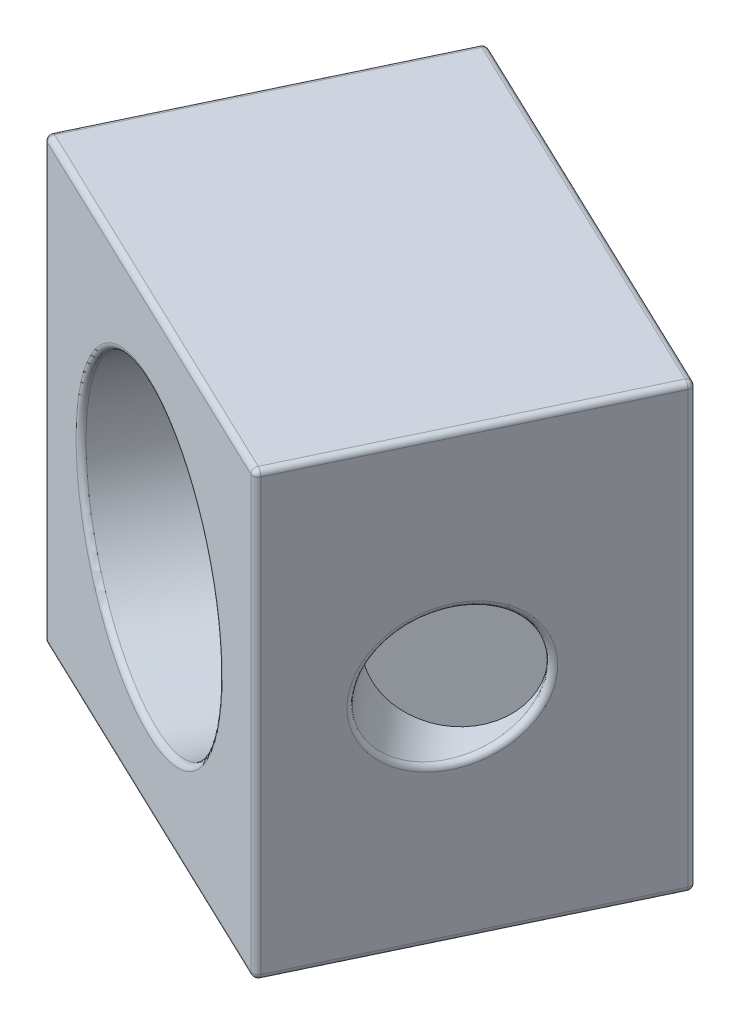
SolidWorks part; units mm, degrees
ref_plane "Front Plane" through (0, 0, 0) normal (0, 0, 1) x (1, 0, 0)
ref_plane "Top Plane" through (0, 0, 0) normal (0, 1, 0) x (1, 0, 0)
ref_plane "Right Plane" through (0, 0, 0) normal (1, 0, 0) x (0, 0, -1)
sketch "Sketch1" plane through (0, 0, 0) normal (0, 1, 0) x (1, 0, 0)
  line L0 (0, 0) -> (640, 0) construction
  line L1 (0, 0) -> (591.2829, 244.9174)
  line L2 (0, 0) -> (591.2829, -244.9174)
  line L3 (0, 0) -> (244.9174, -591.2829)
  line L4 (0, 0) -> (-244.9174, -591.2829)
  line L5 (0, 0) -> (-591.2829, -244.9174)
  line L6 (0, 0) -> (-591.2829, 244.9174)
  line L7 (0, 0) -> (-244.9174, 591.2829)
  line L8 (0, 0) -> (244.9174, 591.2829)
  line L9 (0, 145) -> (55, 145) construction
  line L10 (0, 0) -> (100, 0) construction
  line L11 (0, 0) -> (0, 145) construction
  line L14 (100, 0) -> (100, 145) construction
  circle A0 centre (0, 0) radius 640 construction
  point P15 (0, 0)
  dimension "D1" = 1280
  dimension "D2" = 22.5
  dimension "D4" = 145
  dimension "D5" = 100
  dimension "D6" = 55
  dimension "D3" = 8
sketch "Sketch2" plane through (0, 0, 0) normal (0, 1, 0) x (1, 0, 0)
  line L0 (-486.9956, 169.5033) -> (-66.9956, 169.5033) construction
  line L1 (-188.7141, -86.1278) -> (-188.7141, 241.8722) construction
  line L2 (525.6625, -1048.8053) -> (466.9027, -726.1115) construction
sketch "Sketch3" plane through (0, 0, 0) normal (0, 1, 0) x (1, 0, 0)
  line L0 (0, 0) -> (381.2468, 0) construction
  line L5 (0, 0) -> (0, 199.4415) construction
  line L6 (-10.2736, 158.9263) -> (10.2736, 158.9263)
  line L7 (10.2736, 158.9263) -> (13.1995, 163.9003)
  line L8 (13.1995, 163.9003) -> (45.5131, 148.2994)
  line L9 (45.5131, 148.2994) -> (66.2904, 80.9335)
  line L10 (66.2904, 80.9335) -> (73.8622, 80.9335)
  line L11 (73.8622, 80.9335) -> (86.8684, 42.4396)
  line L12 (86.8684, 42.4396) -> (86.8684, 30.0712)
  line L13 (86.8684, 30.0712) -> (81.3965, 24.5993)
  line L14 (81.3965, 24.5993) -> (81.3965, -24.5993)
  line L15 (-5.8349, 67.4929) -> (5.8349, 67.4929) construction
  line L16 (16.6008, 64.1674) -> (16.6008, 27.6557) construction
  line L17 (16.6008, 27.6557) -> (13.2646, 22.809) construction
  line L18 (13.2646, 22.809) -> (13.2646, -22.809) construction
  line L19 (5.8349, 128.0146) -> (5.8349, 107.4452)
  line L22 (5.8349, 107.4452) -> (9.2702, 107.4452)
  line L25 (9.2702, 107.4452) -> (10.663, 103.7163)
  line L26 (10.663, 103.7163) -> (20.7578, 101.0699)
  line L27 (20.7578, 101.0699) -> (32.199, 111.7601)
  line L28 (32.199, 111.7601) -> (32.199, 123.5038)
  line L29 (32.199, 123.5038) -> (24.9078, 123.5038)
  line L30 (24.9078, 123.5038) -> (13.8412, 132.5856)
  line L31 (13.8412, 132.5856) -> (9.2702, 132.5856)
  line L32 (9.2702, 132.5856) -> (5.8349, 128.0146)
  line L33 (41.9414, 39.7891) -> (51.4866, 54.1602)
  line L34 (51.4866, 54.1602) -> (55.4027, 54.1602)
  line L35 (55.4027, 54.1602) -> (58.1637, 51.3993)
  line L36 (58.1637, 51.3993) -> (58.1637, 43.1872)
  line L37 (58.1637, 43.1872) -> (66.3555, 28.462)
  line L38 (66.3555, 28.462) -> (66.3555, 24.0728)
  line L39 (66.3555, 24.0728) -> (62.2596, 17.9061)
  line L40 (62.2596, 17.9061) -> (47.8497, 18.1669)
  line L41 (47.8497, 18.1669) -> (41.9414, 27.1878)
  line L42 (41.9414, 27.1878) -> (41.9414, 39.7891)
  line L43 (-41.9414, 27.1878) -> (-41.9414, 39.7891)
  line L44 (-47.8497, 18.1669) -> (-41.9414, 27.1878)
  line L45 (-62.2596, 17.9061) -> (-47.8497, 18.1669)
  line L46 (-66.3555, 24.0728) -> (-62.2596, 17.9061)
  line L47 (-66.3555, 28.462) -> (-66.3555, 24.0728)
  line L48 (-58.1637, 43.1872) -> (-66.3555, 28.462)
  line L49 (-58.1637, 51.3993) -> (-58.1637, 43.1872)
  line L50 (-55.4027, 54.1602) -> (-58.1637, 51.3993)
  line L51 (-51.4866, 54.1602) -> (-55.4027, 54.1602)
  line L52 (-41.9414, 39.7891) -> (-51.4866, 54.1602)
  line L53 (-9.2702, 132.5856) -> (-5.8349, 128.0146)
  line L54 (-13.8412, 132.5856) -> (-9.2702, 132.5856)
  line L55 (-24.9078, 123.5038) -> (-13.8412, 132.5856)
  line L56 (-32.199, 123.5038) -> (-24.9078, 123.5038)
  line L57 (-32.199, 111.7601) -> (-32.199, 123.5038)
  line L58 (-20.7578, 101.0699) -> (-32.199, 111.7601)
  line L59 (-10.663, 103.7163) -> (-20.7578, 101.0699)
  line L60 (-9.2702, 107.4452) -> (-10.663, 103.7163)
  line L61 (-5.8349, 107.4452) -> (-9.2702, 107.4452)
  line L62 (-5.8349, 128.0146) -> (-5.8349, 107.4452)
  line L63 (-13.2646, 22.809) -> (-13.2646, -22.809) construction
  line L64 (-16.6008, 27.6557) -> (-13.2646, 22.809) construction
  line L65 (-16.6008, 64.1674) -> (-16.6008, 27.6557) construction
  line L66 (-81.3965, 24.5993) -> (-81.3965, -24.5993)
  line L67 (-86.8684, 30.0712) -> (-81.3965, 24.5993)
  line L68 (-86.8684, 42.4396) -> (-86.8684, 30.0712)
  line L69 (-73.8622, 80.9335) -> (-86.8684, 42.4396)
  line L70 (-66.2904, 80.9335) -> (-73.8622, 80.9335)
  line L71 (-45.5131, 148.2994) -> (-66.2904, 80.9335)
  line L72 (-13.1995, 163.9003) -> (-45.5131, 148.2994)
  line L73 (-10.2736, 158.9263) -> (-13.1995, 163.9003)
  line L74 (-10.2736, -158.9263) -> (-13.1995, -163.9003)
  line L75 (-13.1995, -163.9003) -> (-45.5131, -148.2994)
  line L76 (-45.5131, -148.2994) -> (-66.2904, -80.9335)
  line L77 (-66.2904, -80.9335) -> (-73.8622, -80.9335)
  line L78 (-73.8622, -80.9335) -> (-86.8684, -42.4396)
  line L79 (-86.8684, -42.4396) -> (-86.8684, -30.0712)
  line L80 (-86.8684, -30.0712) -> (-81.3965, -24.5993)
  line L81 (-16.6008, -64.1674) -> (-16.6008, -27.6557) construction
  line L82 (-16.6008, -27.6557) -> (-13.2646, -22.809) construction
  line L83 (-5.8349, -128.0146) -> (-5.8349, -107.4452)
  line L84 (-5.8349, -107.4452) -> (-9.2702, -107.4452)
  line L85 (-9.2702, -107.4452) -> (-10.663, -103.7163)
  line L86 (-10.663, -103.7163) -> (-20.7578, -101.0699)
  line L87 (-20.7578, -101.0699) -> (-32.199, -111.7601)
  line L88 (-32.199, -111.7601) -> (-32.199, -123.5038)
  line L89 (-32.199, -123.5038) -> (-24.9078, -123.5038)
  line L90 (-24.9078, -123.5038) -> (-13.8412, -132.5856)
  line L91 (-13.8412, -132.5856) -> (-9.2702, -132.5856)
  line L92 (-9.2702, -132.5856) -> (-5.8349, -128.0146)
  line L93 (-41.9414, -39.7891) -> (-51.4866, -54.1602)
  line L94 (-51.4866, -54.1602) -> (-55.4027, -54.1602)
  line L95 (-55.4027, -54.1602) -> (-58.1637, -51.3993)
  line L96 (-58.1637, -51.3993) -> (-58.1637, -43.1872)
  line L97 (-58.1637, -43.1872) -> (-66.3555, -28.462)
  line L98 (-66.3555, -28.462) -> (-66.3555, -24.0728)
  line L99 (-66.3555, -24.0728) -> (-62.2596, -17.9061)
  line L100 (-62.2596, -17.9061) -> (-47.8497, -18.1669)
  line L101 (-47.8497, -18.1669) -> (-41.9414, -27.1878)
  line L102 (-41.9414, -27.1878) -> (-41.9414, -39.7891)
  line L103 (41.9414, -27.1878) -> (41.9414, -39.7891)
  line L104 (47.8497, -18.1669) -> (41.9414, -27.1878)
  line L105 (62.2596, -17.9061) -> (47.8497, -18.1669)
  line L106 (66.3555, -24.0728) -> (62.2596, -17.9061)
  line L107 (66.3555, -28.462) -> (66.3555, -24.0728)
  line L108 (58.1637, -43.1872) -> (66.3555, -28.462)
  line L109 (58.1637, -51.3993) -> (58.1637, -43.1872)
  line L110 (55.4027, -54.1602) -> (58.1637, -51.3993)
  line L111 (51.4866, -54.1602) -> (55.4027, -54.1602)
  line L112 (41.9414, -39.7891) -> (51.4866, -54.1602)
  line L113 (9.2702, -132.5856) -> (5.8349, -128.0146)
  line L114 (13.8412, -132.5856) -> (9.2702, -132.5856)
  line L115 (24.9078, -123.5038) -> (13.8412, -132.5856)
  line L116 (32.199, -123.5038) -> (24.9078, -123.5038)
  line L117 (32.199, -111.7601) -> (32.199, -123.5038)
  line L118 (20.7578, -101.0699) -> (32.199, -111.7601)
  line L119 (10.663, -103.7163) -> (20.7578, -101.0699)
  line L120 (9.2702, -107.4452) -> (10.663, -103.7163)
  line L121 (5.8349, -107.4452) -> (9.2702, -107.4452)
  line L122 (5.8349, -128.0146) -> (5.8349, -107.4452)
  line L123 (16.6008, -27.6557) -> (13.2646, -22.809) construction
  line L124 (16.6008, -64.1674) -> (16.6008, -27.6557) construction
  line L125 (-5.8349, -67.4929) -> (5.8349, -67.4929) construction
  line L126 (86.8684, -30.0712) -> (81.3965, -24.5993)
  line L127 (86.8684, -42.4396) -> (86.8684, -30.0712)
  line L128 (73.8622, -80.9335) -> (86.8684, -42.4396)
  line L129 (66.2904, -80.9335) -> (73.8622, -80.9335)
  line L130 (45.5131, -148.2994) -> (66.2904, -80.9335)
  line L131 (13.1995, -163.9003) -> (45.5131, -148.2994)
  line L132 (10.2736, -158.9263) -> (13.1995, -163.9003)
  line L133 (-10.2736, -158.9263) -> (10.2736, -158.9263)
  line L134 (-5.3457, 68.4929) -> (5.3457, 68.4929)
  line L135 (17.6008, 64.1674) -> (17.6008, 27.3448)
  line L136 (17.6008, 27.3448) -> (14.2646, 22.498)
  line L137 (14.2646, 22.498) -> (14.2646, -22.498)
  line L138 (-17.6008, 64.1674) -> (-17.6008, 27.3448)
  line L139 (-17.6008, 27.3448) -> (-14.2646, 22.498)
  line L140 (-5.3457, 68.4929) -> (5.3457, 68.4929) construction
  line L141 (14.2646, 22.498) -> (14.2646, -22.498) construction
  line L142 (17.6008, -27.3448) -> (14.2646, -22.498) construction
  line L143 (17.6008, -64.1674) -> (17.6008, -27.3448) construction
  line L144 (-14.2646, 22.498) -> (-14.2646, -22.498)
  line L145 (17.6008, -64.1674) -> (17.6008, -27.3448)
  line L146 (17.6008, -27.3448) -> (14.2646, -22.498)
  line L147 (-17.6008, -27.3448) -> (-14.2646, -22.498)
  line L148 (-17.6008, -64.1674) -> (-17.6008, -27.3448)
  line L149 (-5.3457, -68.4929) -> (5.3457, -68.4929)
  arc A0 (5.8349, 67.4929) -> (16.6008, 64.0252) centre (10.663, 64.0364) cw construction
  arc A5 (-5.8349, 67.4929) -> (-16.6008, 64.0252) centre (-10.663, 64.0364) ccw construction
  arc A6 (-5.8349, -67.4929) -> (-16.6008, -64.0252) centre (-10.663, -64.0364) cw construction
  arc A7 (5.8349, -67.4929) -> (16.6008, -64.0252) centre (10.663, -64.0364) ccw construction
  arc A8 (-5.3457, 68.4929) -> (-17.6008, 64.0234) centre (-10.663, 64.0364) ccw
  arc A9 (5.3457, 68.4929) -> (17.6008, 64.0234) centre (10.663, 64.0364) cw
  arc A10 (-5.3457, 68.4929) -> (-17.6008, 64.0234) centre (-10.663, 64.0364) ccw construction
  arc A11 (5.3457, -68.4929) -> (17.6008, -64.0234) centre (10.663, -64.0364) ccw
  arc A12 (-5.3457, -68.4929) -> (-17.6008, -64.0234) centre (-10.663, -64.0364) cw
  ellipse E0 centre (11.3851, 149.6854) end of major axis (12.0553, 155.2702) minor radius 3.0047
  ellipse E1 centre (33.6925, 82.363) end of major axis (41.1096, 88.3895) minor radius 4.3287
  ellipse E2 centre (44.8955, 74.0187) end of major axis (51.4866, 79.374) minor radius 4.6847
  ellipse E3 centre (66.3555, 66.447) end of major axis (67.1471, 72.2416) minor radius 3.5711
  ellipse E4 centre (-66.3555, 66.447) end of major axis (-67.1471, 72.2416) minor radius 3.5711
  ellipse E5 centre (-44.8955, 74.0187) end of major axis (-51.4866, 79.374) minor radius 4.6847
  ellipse E6 centre (-33.6925, 82.363) end of major axis (-41.1096, 88.3895) minor radius 4.3287
  ellipse E7 centre (-11.3851, 149.6854) end of major axis (-12.0553, 155.2702) minor radius 3.0047
  ellipse E8 centre (-11.3851, -149.6854) end of major axis (-12.0553, -155.2702) minor radius 3.0047
  ellipse E9 centre (-33.6925, -82.363) end of major axis (-41.1096, -88.3895) minor radius 4.3287
  ellipse E10 centre (-44.8955, -74.0187) end of major axis (-51.4866, -79.374) minor radius 4.6847
  ellipse E11 centre (-66.3555, -66.447) end of major axis (-67.1471, -72.2416) minor radius 3.5711
  ellipse E12 centre (66.3555, -66.447) end of major axis (67.1471, -72.2416) minor radius 3.5711
  ellipse E13 centre (44.8955, -74.0187) end of major axis (51.4866, -79.374) minor radius 4.6847
  ellipse E14 centre (33.6925, -82.363) end of major axis (41.1096, -88.3895) minor radius 4.3287
  ellipse E15 centre (11.3851, -149.6854) end of major axis (12.0553, -155.2702) minor radius 3.0047
  point P117 (0, 67.4929)
  point P126 (0, 158.9263)
  point P180 (0, -158.9263)
  point P181 (0, -67.4929)
  point P190 (-81.3965, 0)
  point P193 (-13.2646, 0)
  point P234 (13.2646, 0)
  point P237 (81.3965, 0)
  point P261 (0, 68.4929)
  point P271 (14.2646, 0)
  point P274 (-14.2646, 0)
  dimension "D1" = 1
sketch "Sketch4" plane through (0, 0, 0) normal (0, 1, 0) x (1, 0, 0)
  line L0 (0, 0) -> (81.2255, 0) construction
  line L1 (0, 0) -> (0, 97.3086) construction
  line L2 (0, 0) -> (0, 199.4415) construction
  line L3 (-10.1399, 86.6928) -> (10.1399, 86.6928)
  line L4 (10.1399, 86.6928) -> (16.0235, 80.8091)
  line L5 (16.0235, 80.8091) -> (23.9736, 57.3032)
  line L6 (23.9736, 57.3032) -> (23.9736, 47.8894)
  line L7 (23.9736, 47.8894) -> (21.6776, 47.8894)
  line L8 (21.6776, 47.8894) -> (21.6776, 27.2256)
  line L9 (21.6776, 27.2256) -> (27.5382, 22.1416)
  line L10 (27.5382, 22.1416) -> (27.5382, 14.9676)
  line L11 (27.5382, 14.9676) -> (23.9736, 10.8585)
  line L12 (23.9736, 10.8585) -> (23.9736, -10.8585)
  line L13 (-23.9736, 10.8585) -> (-23.9736, -10.8585)
  line L14 (-27.5382, 14.9676) -> (-23.9736, 10.8585)
  line L15 (-27.5382, 22.1416) -> (-27.5382, 14.9676)
  line L16 (-21.6776, 27.2256) -> (-27.5382, 22.1416)
  line L17 (-21.6776, 47.8894) -> (-21.6776, 27.2256)
  line L18 (-23.9736, 47.8894) -> (-21.6776, 47.8894)
  line L19 (-23.9736, 57.3032) -> (-23.9736, 47.8894)
  line L20 (-16.0235, 80.8091) -> (-23.9736, 57.3032)
  line L21 (-10.1399, 86.6928) -> (-16.0235, 80.8091)
  line L22 (-10.1399, -86.6928) -> (-16.0235, -80.8091)
  line L23 (-16.0235, -80.8091) -> (-23.9736, -57.3032)
  line L24 (-23.9736, -57.3032) -> (-23.9736, -47.8894)
  line L25 (-23.9736, -47.8894) -> (-21.6776, -47.8894)
  line L26 (-21.6776, -47.8894) -> (-21.6776, -27.2256)
  line L27 (-21.6776, -27.2256) -> (-27.5382, -22.1416)
  line L28 (-27.5382, -22.1416) -> (-27.5382, -14.9676)
  line L29 (-27.5382, -14.9676) -> (-23.9736, -10.8585)
  line L30 (27.5382, -14.9676) -> (23.9736, -10.8585)
  line L31 (27.5382, -22.1416) -> (27.5382, -14.9676)
  line L32 (21.6776, -27.2256) -> (27.5382, -22.1416)
  line L33 (21.6776, -47.8894) -> (21.6776, -27.2256)
  line L34 (23.9736, -47.8894) -> (21.6776, -47.8894)
  line L35 (23.9736, -57.3032) -> (23.9736, -47.8894)
  line L36 (16.0235, -80.8091) -> (23.9736, -57.3032)
  line L37 (10.1399, -86.6928) -> (16.0235, -80.8091)
  line L38 (-10.1399, -86.6928) -> (10.1399, -86.6928)
  point P3 (0, -86.6928)
  point P27 (0, 86.6928)
  point P37 (-23.9736, 0)
  point P38 (23.9736, 0)
sketch "Sketch5" plane through (0, 0, 0) normal (0, 1, 0) x (1, 0, 0)
  line L0 (0, 68.4929) -> (0, 86.6928) construction
  line L1 (15.4511, 110) -> (223.3697, 546.0887)
  line L2 (0, 0) -> (0, 251.8084) construction
  line L3 (0, 110) -> (47.9221, 110) construction
  line L5 (244.9174, 616.9519) -> (262.4572, 609.0616) construction
  line L6 (262.4572, 609.0616) -> (269.1565, 599.6825) construction
  line L7 (269.1565, 599.6825) -> (256.4381, 571.4103) construction
  line L8 (256.4381, 571.4103) -> (244.9174, 563.1812) construction
  line L9 (244.9174, 563.1812) -> (221.08, 517.0826) construction
  line L10 (221.08, 517.0826) -> (201.6817, 527.1134) construction
  line L11 (201.6817, 527.1134) -> (221.6088, 571.4103) construction
  line L12 (221.6088, 571.4103) -> (218.2415, 584.6462) construction
  line L13 (218.2415, 584.6462) -> (232.4366, 616.2011) construction
  line L14 (232.4366, 616.2011) -> (244.9174, 616.9519) construction
  line L15 (244.9174, 591.2829) -> (309.3694, 564.586) construction
  line L16 (269.6266, 526.9284) -> (173.6132, 566.6985) construction
  line L18 (0, 0) -> (107.3069, 0) construction
  dimension "D1" = 110
  dimension "D2" = 50
sketch "Sketch6" plane through (0, 0, 0) normal (0, 1, 0) x (1, 0, 0)
  line L1 (27.9119, 24.7148) -> (544.6401, 226.6863)
  circle A0 centre (0, 0) radius 640 construction
  circle A1 centre (0, 0) radius 640 construction
  circle A3 centre (0, 0) radius 589.9318 construction
  dimension "D1" = 50.0682
sketch "Sketch19" plane through (0, 0, 0) normal (0, 1, 0) x (1, 0, 0)
  line L0 (128.4599, 309.2664) -> (271.805, 137.4916) construction
  line L1 (128.4599, 309.2664) -> (95.7387, 324.8672) construction
  line L2 (128.4599, 309.2664) -> (131.8448, 307.6525) construction
  line L3 (-2.602, 118.6074) -> (205.3166, 554.696)
  line L4 (-2.602, 118.6074) -> (205.3166, 554.696) construction
  line L5 (26.7343, 104.6204) -> (234.6528, 540.7091)
  line L6 (26.7343, 104.6204) -> (234.6528, 540.7091) construction
  line L7 (4.1679, 115.3796) -> (212.0865, 551.4683)
  line L8 (4.1679, 115.3796) -> (212.0865, 551.4683) construction
  line L9 (20.631, 43.3425) -> (537.3592, 245.3139)
  line L10 (32.4624, 13.0726) -> (549.1907, 215.044)
  line L11 (32.4624, 13.0726) -> (549.1907, 215.044) construction
  line L12 (23.3613, 36.3571) -> (540.0895, 238.3286)
  line L13 (23.3613, 36.3571) -> (540.0895, 238.3286) construction
  line L14 (20.631, 43.3425) -> (537.3592, 245.3139) construction
  line L15 (30.1192, 103.0065) -> (238.0378, 539.0952)
  line L16 (30.1192, 103.0065) -> (238.0378, 539.0952) construction
  line L17 (134.9154, 322.8062) -> (138.3004, 321.1923)
  line L18 (134.9154, 322.8062) -> (102.1942, 338.407)
  line L19 (122.0044, 295.7266) -> (125.3893, 294.1127)
  line L20 (122.0044, 295.7266) -> (89.2832, 311.3274)
  line L21 (89.2832, 311.3274) -> (102.1942, 338.407)
  line L22 (21.9961, 39.8498) -> (538.7244, 241.8213)
  line L23 (21.9961, 39.8498) -> (538.7244, 241.8213) construction
  line L24 (33.5042, 101.3926) -> (241.4227, 537.4813)
  line L25 (33.5042, 101.3926) -> (241.4227, 537.4813) construction
  line L26 (138.3004, 321.1923) -> (125.3893, 294.1127)
  dimension "D7" = 15
  dimension "D1" = 12.5
  dimension "D2" = 12.5
  dimension "D3" = 12.5
  dimension "D4" = 12.5
  dimension "D5" = 16.25
  dimension "D6" = 20
  dimension "D8" = 16.25
  dimension "D9" = 15
  dimension "D10" = 20
  dimension "D11" = 20
extrude "Boss-Extrude1" add sketch "Sketch19" along normal blind 20 and the other way blind 20
sweep "Cut-Sweep1" cut path "Sketch5" circular profile diameter 27 parameters "D3"=27
sketch "Sketch33" plane through (0, 0, 0) normal (0, 1, 0) x (1, 0, 0)
  line L0 (128.4599, 309.2664) -> (271.805, 137.4916)
sweep "Cut-Sweep2" cut path "Sketch33" circular profile diameter 12 parameters "D3"=12
fillet "Fillet1" radius 0.5 15 edges at (108.0615, 0, -335.6096) (120.2473, -20, -329.7996) (107.3362, -20, -302.72) (119.5221, 0, -296.9101) (131.8448, -20, -307.6525) (125.3893, 0, -294.1127) (138.3004, 0, -321.1923) (128.2623, 0, -300.1385) (131.8448, 20, -307.6525) (107.3362, 20, -302.72) (120.2473, 20, -329.7996) (95.7387, -20, -324.8672) (102.1942, 0, -338.407) (95.7387, 20, -324.8672) (89.2832, 0, -311.3274)
